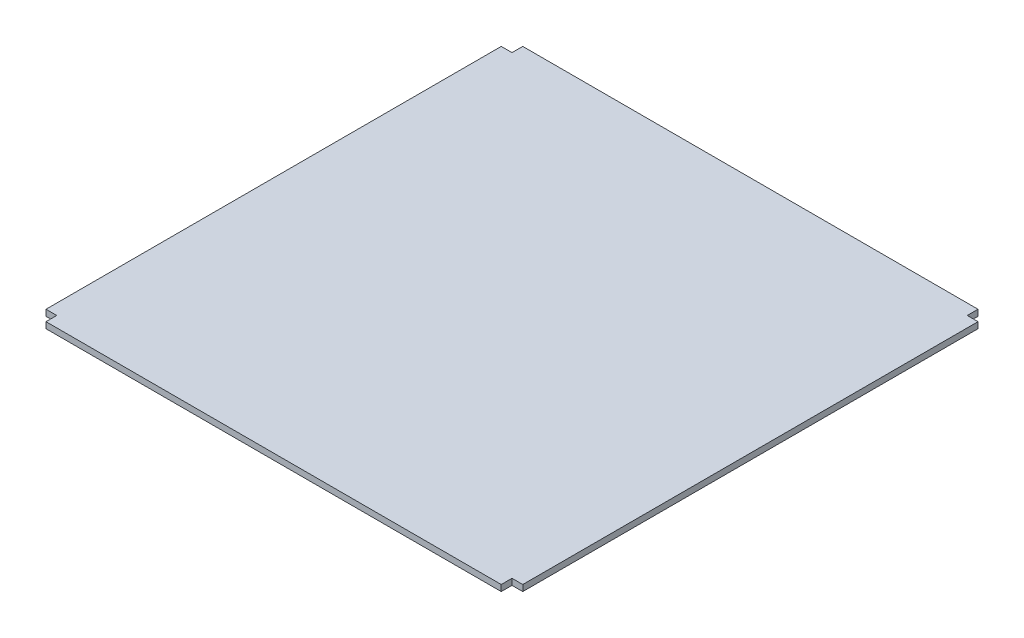
SolidWorks part; units mm, degrees
material "PVC 僵硬"
ref_plane "前视基准面" through (0, 0, 0) normal (0, 0, 1) x (1, 0, 0)
ref_plane "上视基准面" through (0, 0, 0) normal (0, 1, 0) x (1, 0, 0)
ref_plane "右视基准面" through (0, 0, 0) normal (1, 0, 0) x (0, 0, -1)
sketch "草图1" plane through (0, 0, 0) normal (0, 1, 0) x (1, 0, 0)
  line L1 (-155, -155) -> (155, -155)
  line L2 (-155, -155) -> (-155, 155)
  line L3 (-155, 155) -> (155, 155)
  line L4 (155, -155) -> (155, 155)
  line L5 (-155, -155) -> (155, 155) construction
  line L6 (-155, 155) -> (155, -155) construction
  point P0 (0, 0)
  dimension "D1" = 310
  dimension "D2" = 310
extrude "凸台-拉伸1" add sketch "草图1" along normal blind 4
sketch "草图2" plane through (0, 4, 0) normal (0, 1, 0) x (1, 0, 0)
  line L1 (155, -155) -> (148, -155)
  line L2 (155, -155) -> (155, -148)
  line L3 (155, -148) -> (148, -148)
  line L4 (148, -155) -> (148, -148)
  dimension "D1" = 7
  dimension "D2" = 7
extrude "切除-拉伸1" cut sketch "草图2" against normal blind 6
ref_axis "基准轴1" through (0, 0, 0) along (0, 1, 0)
pattern_circular "阵列(圆周)1" count 4 over 360 about axis through (0, 0, 0) along (0, 1, 0) of "切除-拉伸1"
